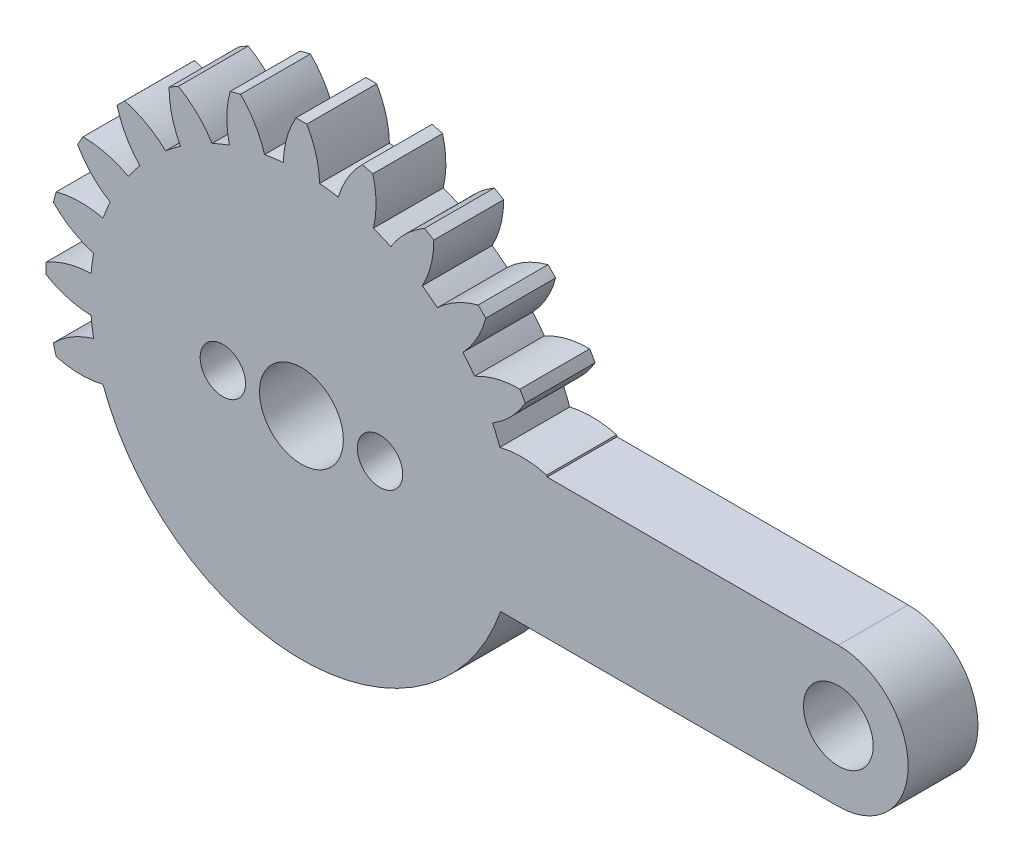
SolidWorks part; units mm, degrees
ref_plane "Front Plane" through (0, 0, 0) normal (0, 0, 1) x (1, 0, 0)
ref_plane "Top Plane" through (0, 0, 0) normal (0, 1, 0) x (1, 0, 0)
ref_plane "Right Plane" through (0, 0, 0) normal (1, 0, 0) x (0, 0, -1)
sketch "Sketch2" plane through (0, 0, 0) normal (0, 0, 1) x (1, 0, 0)
  line L0 (0, 0) -> (0, 14.63) construction
  line L1 (0, 0) -> (34.75, 0) construction
  line L2 (11.4091, 4) -> (30.75, 4)
  line L3 (30.75, -4) -> (11.4091, -4)
  circle A0 centre (0, 0) radius 14.63
  circle A1 centre (0, 0) radius 12.09
  circle A2 centre (0, 0) radius 1.75
  arc A3 (-0.31, 14.6267) -> (-1.04, 12.0452) centre (4.3584, 11.9126) ccw
  arc A4 (0.31, 14.6267) -> (1.04, 12.0452) centre (-4.3584, 11.9126) cw
  arc A5 (3.4862, 14.2086) -> (2.113, 11.9039) centre (7.2931, 10.3787) ccw
  arc A6 (4.0851, 14.0481) -> (4.1221, 11.3656) centre (-1.1267, 12.6347) cw
  arc A7 (7.0449, 12.8221) -> (5.1219, 10.9514) centre (9.7308, 8.1374) ccw
  arc A8 (7.5818, 12.5121) -> (6.9233, 9.9114) centre (2.1819, 12.4958) cw
  arc A9 (10.1234, 10.5619) -> (7.7818, 9.2526) centre (11.5053, 5.3417) ccw
  arc A10 (10.5619, 10.1234) -> (9.2526, 7.7818) centre (5.3417, 11.5053) cw
  arc A11 (12.5121, 7.5818) -> (9.9114, 6.9233) centre (12.4958, 2.1819) ccw
  arc A12 (12.8221, 7.0449) -> (10.9514, 5.1219) centre (8.1374, 9.7308) cw
  arc A13 (14.0481, 4.0851) -> (11.3656, 4.1221) centre (12.6347, -1.1267) ccw
  arc A14 (14.2086, 3.4862) -> (11.9039, 2.113) centre (10.3787, 7.2931) cw
  arc A15 (14.6267, 0.31) -> (12.0452, 1.04) centre (11.9126, -4.3584) ccw
  arc A16 (14.6267, -0.31) -> (12.0452, -1.04) centre (11.9126, 4.3584) cw
  arc A17 (14.2086, -3.4862) -> (11.9039, -2.113) centre (10.3787, -7.2931) ccw
  arc A18 (14.0481, -4.0851) -> (11.3656, -4.1221) centre (12.6347, 1.1267) cw
  arc A19 (12.8221, -7.0449) -> (10.9514, -5.1219) centre (8.1374, -9.7308) ccw
  arc A20 (12.5121, -7.5818) -> (9.9114, -6.9233) centre (12.4958, -2.1819) cw
  arc A21 (10.5619, -10.1234) -> (9.2526, -7.7818) centre (5.3417, -11.5053) ccw
  arc A22 (10.1234, -10.5619) -> (7.7818, -9.2526) centre (11.5053, -5.3417) cw
  arc A23 (7.5818, -12.5121) -> (6.9233, -9.9114) centre (2.1819, -12.4958) ccw
  arc A24 (7.0449, -12.8221) -> (5.1219, -10.9514) centre (9.7308, -8.1374) cw
  arc A25 (4.0851, -14.0481) -> (4.1221, -11.3656) centre (-1.1267, -12.6347) ccw
  arc A26 (3.4862, -14.2086) -> (2.113, -11.9039) centre (7.2931, -10.3787) cw
  arc A27 (0.31, -14.6267) -> (1.04, -12.0452) centre (-4.3584, -11.9126) ccw
  arc A28 (-0.31, -14.6267) -> (-1.04, -12.0452) centre (4.3584, -11.9126) cw
  arc A29 (-3.4862, -14.2086) -> (-2.113, -11.9039) centre (-7.2931, -10.3787) ccw
  arc A30 (-4.0851, -14.0481) -> (-4.1221, -11.3656) centre (1.1267, -12.6347) cw
  arc A31 (-7.0449, -12.8221) -> (-5.1219, -10.9514) centre (-9.7308, -8.1374) ccw
  arc A32 (-7.5818, -12.5121) -> (-6.9233, -9.9114) centre (-2.1819, -12.4958) cw
  arc A33 (-10.1234, -10.5619) -> (-7.7818, -9.2526) centre (-11.5053, -5.3417) ccw
  arc A34 (-10.5619, -10.1234) -> (-9.2526, -7.7818) centre (-5.3417, -11.5053) cw
  arc A35 (-12.5121, -7.5818) -> (-9.9114, -6.9233) centre (-12.4958, -2.1819) ccw
  arc A36 (-12.8221, -7.0449) -> (-10.9514, -5.1219) centre (-8.1374, -9.7308) cw
  arc A37 (-14.0481, -4.0851) -> (-11.3656, -4.1221) centre (-12.6347, 1.1267) ccw
  arc A38 (-14.2086, -3.4862) -> (-11.9039, -2.113) centre (-10.3787, -7.2931) cw
  arc A39 (-14.6267, -0.31) -> (-12.0452, -1.04) centre (-11.9126, 4.3584) ccw
  arc A40 (-14.6267, 0.31) -> (-12.0452, 1.04) centre (-11.9126, -4.3584) cw
  arc A41 (-14.2086, 3.4862) -> (-11.9039, 2.113) centre (-10.3787, 7.2931) ccw
  arc A42 (-14.0481, 4.0851) -> (-11.3656, 4.1221) centre (-12.6347, -1.1267) cw
  arc A43 (-12.8221, 7.0449) -> (-10.9514, 5.1219) centre (-8.1374, 9.7308) ccw
  arc A44 (-12.5121, 7.5818) -> (-9.9114, 6.9233) centre (-12.4958, 2.1819) cw
  arc A45 (-10.5619, 10.1234) -> (-9.2526, 7.7818) centre (-5.3417, 11.5053) ccw
  arc A46 (-10.1234, 10.5619) -> (-7.7818, 9.2526) centre (-11.5053, 5.3417) cw
  arc A47 (-7.5818, 12.5121) -> (-6.9233, 9.9114) centre (-2.1819, 12.4958) ccw
  arc A48 (-7.0449, 12.8221) -> (-5.1219, 10.9514) centre (-9.7308, 8.1374) cw
  arc A49 (-4.0851, 14.0481) -> (-4.1221, 11.3656) centre (1.1267, 12.6347) ccw
  arc A50 (-3.4862, 14.2086) -> (-2.113, 11.9039) centre (-7.2931, 10.3787) cw
  arc A51 (30.75, 4) -> (30.75, -4) centre (30.75, 0) cw
  circle A52 centre (30.75, 0) radius 1.995
  point P154 (0, 0)
  dimension "D1" = 3.5
  dimension "D2" = 24.18
  dimension "D3" = 29.26
  dimension "D4" = 0.62
  dimension "D6" = 5.4
  dimension "D8" = 30.75
  dimension "D9" = 4
  dimension "D10" = 3.99
  dimension "D5" = 2.08
  dimension "D7" = 24
extrude "Boss-Extrude1" add sketch "Sketch2" along normal blind 4 contours A1 | A0 A13 A1 L2 | A14 A0 L2 A1 | A15 A0 A14 A1 | A16 A0 A15 A1 | A17 A0 A16 A1 | A0 A17 A1 L3 | A51 L2 A0 L3 A52 | A12 A0 A11 A1 | A38 A0 A37 A1 | A40 A0 A39 A1 | A42 A0 A41 A1 | A44 A0 A43 A1 | A46 A0 A45 A1 | A48 A0 A47 A1 | A50 A0 A49 A1 | A4 A0 A3 A1 | A6 A0 A5 A1 | A8 A0 A7 A1 | A10 A0 A9 A1 region at (12.6776, 4.1147, 0) region at (12.7147, 3.2863, 0) region at (11.3639, 2.9797, 0) region at (23.6149, 0, 0) region at (13.463, 1.7724, 0) region at (13.1577, 0, 0) region at (11.3949, 6.5788, 0) region at (12.7147, -3.2863, 0) region at (13.463, -1.7724, 0) region at (9.3039, 9.3039, 0) region at (6.5788, 11.3949, 0) region at (3.4055, 12.7093, 0) region at (0, 13.1577, 0) region at (-3.4055, 12.7093, 0) region at (-6.5788, 11.3949, 0) region at (-9.3039, 9.3039, 0) region at (-11.3949, 6.5788, 0) region at (-12.7093, 3.4055, 0) region at (-13.1577, 0, 0) region at (-12.7093, -3.4055, 0)
sketch "Sketch4" plane through (0, 0, 4) normal (0, 0, 1) x (1, 0, 0)
  circle A0 centre (4.5, 0) radius 1.3
  circle A1 centre (-4.5, 0) radius 1.3
  circle A2 centre (0, 0) radius 2.4
  dimension "D1" = 4.5
  dimension "D3" = 2.6
  dimension "D4" = 4.8
  dimension "D2" = 9
extrude "Cut-Extrude1" cut sketch "Sketch4" against normal through all
ref_axis "Axis1" through (0, 0, -7.987) along (0, 0, 1)
sketch "Sketch6" plane through (0, 0, 4) normal (0, 0, 1) x (1, 0, 0)
  circle A0 centre (0, 0) radius 13.45 construction
